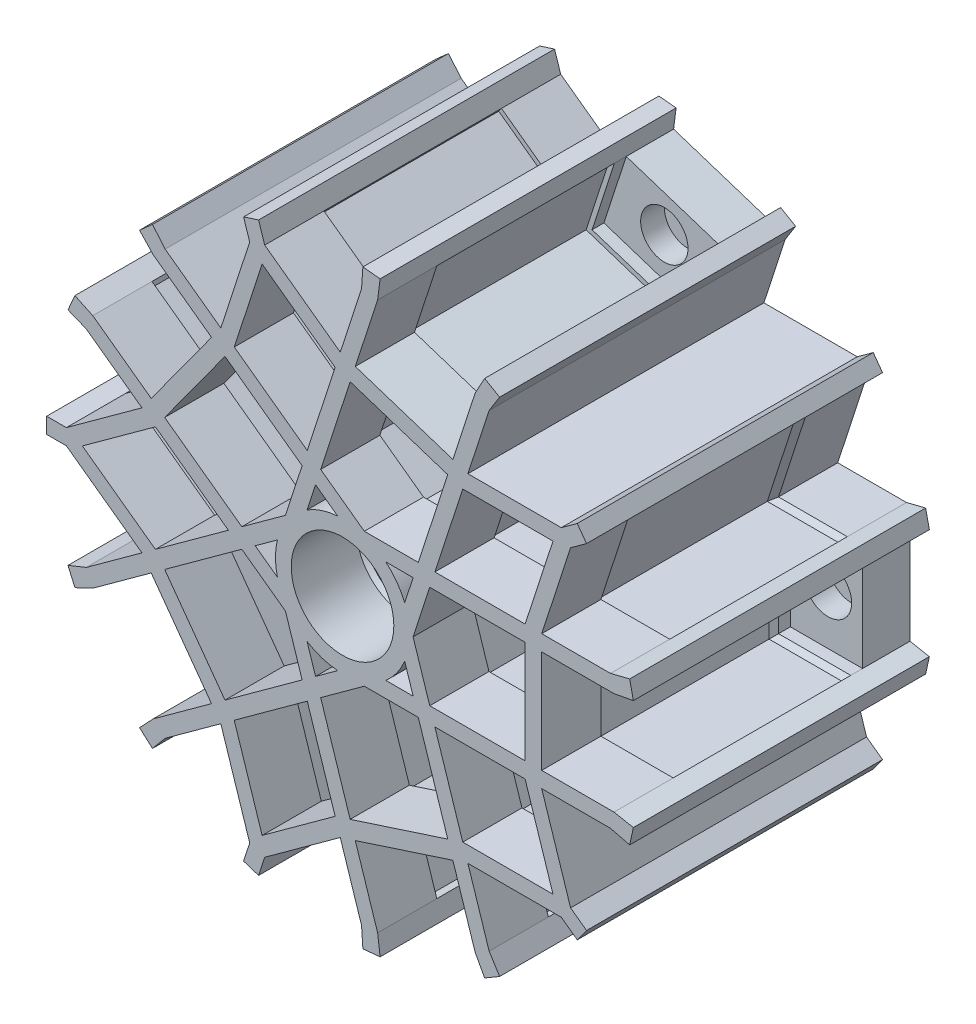
SolidWorks part; units mm, degrees
ref_plane "Front Plane" through (0, 0, 0) normal (0, 0, 1) x (1, 0, 0)
ref_plane "Top Plane" through (0, 0, 0) normal (0, 1, 0) x (1, 0, 0)
ref_plane "Right Plane" through (0, 0, 0) normal (1, 0, 0) x (0, 0, -1)
sketch "Sketch1" plane through (0, 0, 0) normal (0, 0, 1) x (1, 0, 0)
  circle A0 centre (0, 0) radius 13
  circle A1 centre (0, 0) radius 17
  dimension "D1" = 26
  dimension "D2" = 34
extrude "Boss-Extrude1" add sketch "Sketch1" along normal mid plane 75
sketch "Sketch2" plane through (0, 0, 0) normal (0, 0, 1) x (1, 0, 0)
  line L0 (0, 17) -> (0, 13)
  line L1 (0, 13) -> (68.7823, 13)
  line L2 (0, 17) -> (67.9043, 17)
  line L3 (68.7823, 13) -> (73.6953, 13.9286)
  line L4 (67.9043, 17) -> (72.7547, 18.2143)
  line L5 (72.7547, 18.2143) -> (73.6953, 13.9286)
  line L6 (0, 0) -> (70, 0) construction
  line L7 (68.7823, -13) -> (73.6953, -13.9286)
  line L8 (72.7547, -18.2143) -> (73.6953, -13.9286)
  line L9 (67.9043, -17) -> (72.7547, -18.2143)
  line L10 (0, -13) -> (68.7823, -13)
  line L11 (0, -17) -> (67.9043, -17)
  line L12 (0, -17) -> (0, -13)
  circle A0 centre (0, 0) radius 70 construction
  circle A1 centre (0, 0) radius 17 construction
  circle A2 centre (0, 0) radius 13 construction
  circle A3 centre (0, 0) radius 75 construction
  dimension "D1" = 140
  dimension "D2" = 150
extrude "Boss-Extrude2" add sketch "Sketch2" along normal mid plane 75
ref_axis "Axis1" through (0, 0, -41.25) along (0, 0, 1)
pattern_circular "CirPattern1" count 5 over 360 about axis through (0, 0, -41.25) along (0, 0, 1) of "Boss-Extrude2"
sketch "Sketch3" plane through (0, 0, 0) normal (0, 0, 1) x (1, 0, 0)
  line L0 (0, 0) -> (70, 0) construction
  line L1 (0, 0) -> (56.6312, 41.145) construction
  line L2 (56.6312, 0) -> (56.6312, -41.145) construction
  line L3 (55.4325, 42.7462) -> (59.4791, 45.6863)
  line L4 (57.7836, 39.5101) -> (61.8303, 42.4502)
  line L6 (46.2638, 17) -> (46.2638, -13)
  line L7 (59.4791, 45.6863) -> (61.8303, 42.4502)
  line L8 (55.4325, 42.7462) -> (31.7639, 42.7462)
  line L9 (23.3985, 17) -> (37.1516, 59.3276) construction
  line L10 (31.7639, 42.7462) -> (30.4643, 38.7462)
  line L11 (30.4643, 38.7462) -> (53.3296, 38.7462)
  line L14 (46.2638, 17) -> (53.3296, 38.7462)
  line L16 (57.7836, 39.5101) -> (50.4697, 17)
  line L17 (68.7823, -13) -> (22.0988, -13) construction
  line L18 (50.4697, 17) -> (50.4697, -13)
  line L19 (50.4697, -13) -> (46.2638, -13)
  circle A0 centre (0, 0) radius 70 construction
  circle A1 centre (0, 0) radius 75 construction
  dimension "D1" = 140
  dimension "D2" = 150
  dimension "D3" = 36
  dimension "D4" = 2
  dimension "D7" = 4
extrude "Boss-Extrude3" add sketch "Sketch3" along normal mid plane 75
pattern_circular "CirPattern2" count 5 over 360 about axis through (0, 0, -41.25) along (0, 0, 1) of "Boss-Extrude3"
sketch "Sketch4" plane through (0, 0, 0) normal (0, 0, 1) x (1, 0, 0)
  circle A0 centre (0, 0) radius 13
  circle A1 centre (0, 0) radius 5.5
  dimension "D1" = 11
extrude "Boss-Extrude4" add sketch "Sketch4" along normal mid plane 40
chamfer "Chamfer1" distance 1 angle 45 2 edges at (13, 0, -20) (13, 0, 20)
sketch "Sketch9" plane through (0, 0, 0) normal (0, 0, 1) x (1, 0, 0)
  line L0 (68.7823, -13) -> (50.4697, -13) construction
  line L1 (50.4697, 13) -> (68.7823, 13) construction
  line L2 (67.9043, 17) -> (50.4697, 17) construction
  line L3 (10.9545, 13) -> (17.893, 13) construction
  line L4 (17.893, 13) -> (15.7488, 6.4011) construction
  line L5 (50.4697, 17) -> (57.7836, 39.5101) construction
  line L6 (53.3296, 38.7462) -> (46.2638, 17) construction
  line L7 (30.4643, 38.7462) -> (53.3296, 38.7462) construction
  line L8 (23.3985, 17) -> (30.4643, 38.7462) construction
  line L9 (46.2638, 17) -> (23.3985, 17) construction
  line L10 (50.4697, -13) -> (50.4697, 13) construction
  line L11 (22.0988, -13) -> (17.8749, 0) construction
  line L12 (46.2638, -13) -> (22.0988, -13) construction
  line L13 (46.2638, 13) -> (46.2638, -13) construction
  line L14 (22.0988, 13) -> (46.2638, 13) construction
  line L15 (17.8749, 0) -> (22.0988, 13) construction
  line L16 (68.7823, -13) -> (50.4697, -13) construction
  line L17 (50.4697, 13) -> (68.7823, 13) construction
  line L18 (67.9043, 17) -> (50.4697, 17) construction
  line L19 (10.9545, 13) -> (17.893, 13) construction
  line L20 (17.893, 13) -> (15.7488, 6.4011) construction
  line L21 (50.4697, 17) -> (57.7836, 39.5101) construction
  line L22 (53.3296, 38.7462) -> (46.2638, 17) construction
  line L23 (30.4643, 38.7462) -> (53.3296, 38.7462) construction
  line L24 (23.3985, 17) -> (30.4643, 38.7462) construction
  line L25 (46.2638, 17) -> (23.3985, 17) construction
  line L26 (50.4697, -13) -> (50.4697, 13) construction
  line L27 (22.0988, -13) -> (17.8749, 0) construction
  line L28 (46.2638, -13) -> (22.0988, -13) construction
  line L29 (46.2638, 13) -> (46.2638, -13) construction
  line L30 (22.0988, 13) -> (46.2638, 13) construction
  line L31 (17.8749, 0) -> (22.0988, 13) construction
  line L32 (6.9282, 14.2) -> (19.5446, 14.2)
  line L33 (19.5446, 14.2) -> (15.6459, 2.2011)
  line L34 (54.9812, 39.9462) -> (47.1357, 15.8)
  line L35 (47.1357, 15.8) -> (21.7468, 15.8)
  line L36 (21.7468, 15.8) -> (29.5924, 39.9462)
  line L37 (29.5924, 39.9462) -> (54.9812, 39.9462)
  line L38 (21.227, -14.2) -> (16.6131, 0)
  line L39 (16.6131, 0) -> (21.227, 14.2)
  line L40 (21.227, 14.2) -> (47.4638, 14.2)
  line L41 (47.4638, 14.2) -> (47.4638, -14.2)
  line L42 (47.4638, -14.2) -> (21.227, -14.2)
  line L43 (67.4984, 15.8) -> (48.818, 15.8)
  line L44 (48.818, 15.8) -> (56.6424, 39.881)
  line L45 (68.0259, -14.2) -> (49.2697, -14.2)
  line L46 (49.2697, -14.2) -> (49.2697, 14.2)
  line L47 (49.2697, 14.2) -> (68.0259, 14.2)
  line L48 (56.6424, 39.881) -> (57.7836, 39.5101)
  line L49 (57.7836, 39.5101) -> (67.9043, 17)
  line L52 (68.7823, 13) -> (68.7823, -13)
  line L54 (49.2697, 14.2) -> (68.7823, 14.2) construction
  line L55 (67.9043, 15.8) -> (48.818, 15.8) construction
  line L56 (67.4984, 15.8) -> (67.9043, 17)
  line L57 (68.0259, 14.2) -> (68.7823, 13)
  line L58 (68.7823, -14.2) -> (49.2697, -14.2) construction
  line L59 (68.0259, -14.2) -> (68.7823, -13)
  arc A0 (15.7488, 6.4011) -> (10.9545, 13) centre (0, 0) ccw construction
  arc A1 (15.7488, 6.4011) -> (10.9545, 13) centre (0, 0) ccw construction
  arc A2 (15.6459, 2.2011) -> (6.9282, 14.2) centre (0, 0) ccw
  dimension "D1" = 1.2
  dimension "D2" = 1.2
extrude "Cut-Extrude2" cut sketch "Sketch9" against normal mid plane 45
chamfer "Chamfer3" distance 1.2 angle 45 14 edges at (51.0584, 27.8731, -22.5) (42.2868, 39.9462, -22.5) (25.6696, 27.8731, -22.5) (34.4412, 15.8, -22.5) (18.92, 7.1, -22.5) (18.92, -7.1, -22.5) (34.3454, 14.2, -22.5) (47.4638, 0, -22.5) (34.3454, -14.2, -22.5) (58.1582, 15.8, -22.5) (52.7302, 27.8405, -22.5) (58.6478, 14.2, -22.5) (49.2697, 0, -22.5) (58.6478, -14.2, -22.5)
pattern_circular "CirPattern3" count 5 over 360 about axis through (0, 0, -41.25) along (0, 0, 1) of "Cut-Extrude2"
sketch "Sketch10" plane through (0, 0, -37.5) normal (0, 0, -1) x (-1, 0, 0)
  line L0 (0, 0) -> (-60, 0) construction
  line L1 (-50.4697, 13) -> (-50.4697, -13)
  line L2 (-50.4697, -13) -> (-68.7823, -13)
  line L3 (-68.7823, -13) -> (-68.7823, 13)
  line L4 (-68.7823, 13) -> (-50.4697, 13)
  circle A0 centre (-60, 0) radius 2.5
  circle A1 centre (0, 0) radius 70 construction
  dimension "D2" = 5
  dimension "D3" = 140
  dimension "D1" = 60
extrude "Boss-Extrude5" add sketch "Sketch10" against normal blind 12
sketch "Sketch11" plane through (0, 0, -25.5) normal (0, 0, 1) x (1, 0, 0)
  circle A0 centre (60, 0) radius 6
  dimension "D1" = 12
extrude "Cut-Extrude3" cut sketch "Sketch11" against normal blind 6
pattern_circular "CirPattern4" count 5 over 360 about axis through (0, 0, -41.25) along (0, 0, 1) of "Boss-Extrude5", "Cut-Extrude3"
sketch "Sketch12" plane through (0, 0, -37.5) normal (0, 0, -1) x (-1, 0, 0)
  line L0 (-25, 0) -> (-25, 13) construction
  line L1 (-22.0988, 13) -> (-46.2638, 13) construction
  line L2 (-22.0988, -13) -> (-17.8749, 0) construction
  line L3 (-17.8749, 0) -> (-22.0988, 13) construction
  line L4 (-22.0988, -13) -> (-17.8749, 0)
  line L5 (-17.8749, 0) -> (-22.0988, 13)
  line L6 (-27.9012, -13) -> (-32.1251, 0)
  line L7 (-32.1251, 0) -> (-27.9012, 13)
  line L8 (-27.9012, 13) -> (-22.0988, 13)
  line L9 (-27.9012, -13) -> (-22.0988, -13)
  circle A0 centre (-25, 0) radius 2.5
  dimension "D1" = 5
  dimension "D2" = 25
extrude "Boss-Extrude6" add sketch "Sketch12" against normal blind 10
pattern_circular "CirPattern5" count 5 over 360 about axis through (0, 0, -41.25) along (0, 0, 1) of "Boss-Extrude6"
